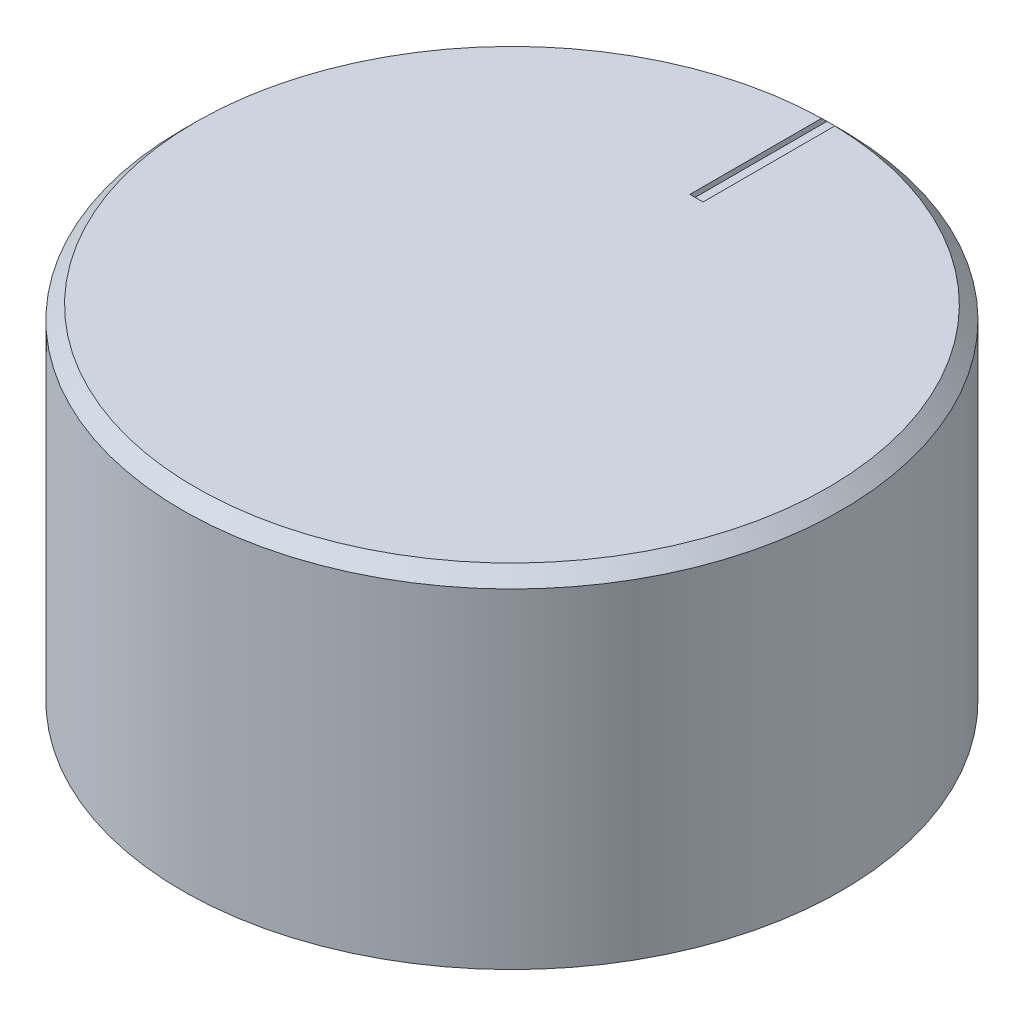
SolidWorks part; units mm, degrees
ref_plane "Front Plane" through (0, 0, 0) normal (0, 0, 1) x (1, 0, 0)
ref_plane "Top Plane" through (0, 0, 0) normal (0, 1, 0) x (1, 0, 0)
ref_plane "Right Plane" through (0, 0, 0) normal (1, 0, 0) x (0, 0, -1)
ref_plane "Plane1" through (0, 0, 0) normal (0, 0, -1) x (-1, 0, 0)
sketch "Sketch1" plane through (0, 0, 0) normal (0, 0, -1) x (-1, 0, 0)
  line L0 (-12.5, 0) -> (0, 0)
  line L1 (0, 0) -> (0, 13)
  line L2 (0, 13) -> (-12.5, 13)
  line L3 (-12.5, 13) -> (-12.5, 0)
  line L4 (0, 0) -> (0, 13) construction
revolve "Revolve1" add sketch "Sketch1" angle 360 about L4 reverse direction yes
sketch "Sketch2" plane through (0, 13, 0) normal (0, 1, 0) x (-1, 0, 0)
  line L0 (0.25, -12.4975) -> (0.25, -7)
  line L1 (0.25, -7) -> (-0.25, -7)
  line L2 (-0.25, -7) -> (-0.25, -12.4975)
  arc A0 (-0.25, -12.4975) -> (0.25, -12.4975) centre (0, 0) ccw
extrude "Cut-Extrude1" cut sketch "Sketch2" against normal blind 0.2
hole_wizard "Ø5.0 (5) Diameter Hole1" positions "Sketch4" profile "Sketch3" hole size "Ø5.0" standard "ANSI Metric"
sketch "Sketch4" plane through (0, 0, 0) normal (0, -1, 0) x (-1, 0, 0)
  point P0 (0, 0)
sketch "Sketch3" plane through (0, 0, 0) normal (1, 0, 0) x (0, 0, -1)
  line L0 (0, 0) -> (0, 9)
  line L1 (0, 9) -> (2.5, 9)
  line L2 (2.5, 9) -> (2.5, 0)
  line L5 (2.5, 0) -> (0, 0)
  line L10 (0, 9) -> (-2.5, 9) construction
  line L11 (0, -6.35) -> (0, 107.95) construction
  dimension "Hole Dia." = 5
  dimension "Hole Depth" = 9
  dimension "Drill Angle" = 180
chamfer "Chamfer1" distance 0.2 angle 45 1 edges at (0, 13, 12.5)
sketch "Sketch5" plane through (0, 13, 0) normal (0, 1, 0) x (-1, 0, 0)
  line L0 (0.25, -7) -> (-0.25, -7)
  line L1 (-0.25, -12.4975) -> (-0.25, -7)
  line L2 (0.25, -7) -> (0.25, -12.4975)
  arc A0 (0.25, -12.4975) -> (-0.25, -12.4975) centre (0, 0) ccw
  circle A1 centre (0, 0) radius 2.5
extrude "Boss-Extrude1" add sketch "Sketch5" against normal blind 10
chamfer "Chamfer2" distance 0.5 angle 45 1 edges at (0, 13, 12.5)
